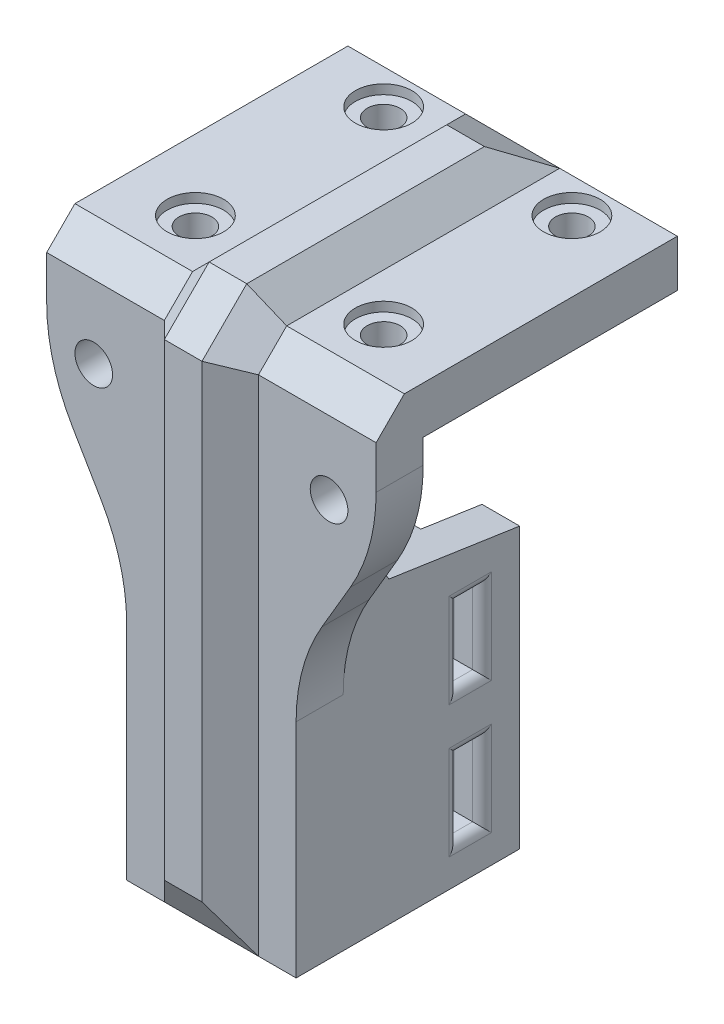
SolidWorks part; units mm, degrees
material "ABS"
ref_plane "Front Plane" through (0, 0, 0) normal (0, 0, 1) x (1, 0, 0)
ref_plane "Top Plane" through (0, 0, 0) normal (0, 1, 0) x (1, 0, 0)
ref_plane "Right Plane" through (0, 0, 0) normal (1, 0, 0) x (0, 0, -1)
sketch "Sketch1" plane through (0, 0, 0) normal (1, 0, 0) x (0, 0, -1)
  line L0 (0, 0) -> (0, -56.5)
  line L1 (0, 0) -> (32, 0)
  line L2 (32, 0) -> (32, -5)
  line L3 (32, -5) -> (5, -5)
  line L4 (5, -5) -> (5, -56.5)
  line L5 (5, -56.5) -> (0, -56.5)
  dimension "D1" = 5
  dimension "D2" = 27
  dimension "D3" = 51.5
extrude "Boss-Extrude1" add sketch "Sketch1" along normal blind 17.5 and the other way blind 17.5
sketch "Sketch2" plane through (0, 0, -5) normal (0, 0, -1) x (-1, 0, 0)
  line L0 (-39.6629, -48.5) -> (3.2968, -48.5) construction
  line L1 (-17.5, -5) -> (17.5, -5) construction
  line L2 (3.2968, -34.5) -> (-37.6565, -34.5) construction
  line L3 (-24.2611, -24) -> (31.917, -24) construction
  line L4 (-17.5, -56.5) -> (-17.5, -5) construction
  line L5 (-17.5, -27.5) -> (17.5, -27.5)
  line L6 (-17.5, -27.5) -> (-17.5, -56.5)
  line L7 (-17.5, -56.5) -> (17.5, -56.5)
  line L8 (17.5, -27.5) -> (17.5, -56.5)
  dimension "D1" = 14
  dimension "D2" = 43.5
  dimension "D3" = 19
  dimension "D4" = 7
extrude "Boss-Extrude2" add sketch "Sketch2" along normal blind 23.5
sketch "Sketch3" plane through (17.5, 0, 0) normal (1, 0, 0) x (0, 0, -1)
  line L0 (5, -27.5) -> (5, -5) construction
  line L1 (17.25, -30.5) -> (19.75, -30.5)
  line L2 (17.25, -30.5) -> (17.25, -38.5)
  line L3 (17.25, -38.5) -> (19.75, -38.5)
  line L4 (19.75, -30.5) -> (19.75, -38.5)
  line L5 (17.25, -30.5) -> (19.75, -38.5) construction
  line L6 (17.25, -38.5) -> (19.75, -30.5) construction
  line L7 (17.25, -44.5) -> (19.75, -44.5)
  line L8 (17.25, -44.5) -> (17.25, -52.5)
  line L9 (17.25, -52.5) -> (19.75, -52.5)
  line L10 (19.75, -44.5) -> (19.75, -52.5)
  line L11 (17.25, -44.5) -> (19.75, -52.5) construction
  line L12 (17.25, -52.5) -> (19.75, -44.5) construction
  line L13 (5, -5) -> (32, -5) construction
  point P0 (18.5, -34.5)
  point P5 (18.5, -48.5)
  dimension "D1" = 13.5
  dimension "D2" = 14
  dimension "D3" = 43.5
  dimension "D4" = 2.5
  dimension "D5" = 8
extrude "Cut-Extrude1" cut sketch "Sketch3" against normal through all
sketch "Sketch4" plane through (0, 0, -28.5) normal (0, 0, -1) x (-1, 0, 0)
  line L0 (-17.5, -27.5) -> (17.5, -27.5) construction
  line L1 (-5, -27.5) -> (5, -27.5)
  line L2 (-5, -27.5) -> (-5, -56.5)
  line L3 (-5, -56.5) -> (5, -56.5)
  line L4 (5, -27.5) -> (5, -56.5)
  line L5 (-17.5, -56.5) -> (17.5, -56.5) construction
  line L6 (-17.5, 0) -> (17.5, 0) construction
  point P8 (0, -27.5)
  point P11 (0, 0)
  dimension "D1" = 10
extrude "Cut-Extrude2" cut sketch "Sketch4" against normal up to surface (11.25 mm away) up to face at (0, -34.5, -17.25)
sketch "Sketch5" plane through (0, 0, -28.5) normal (0, 0, -1) x (-1, 0, 0)
  line L0 (-9, -27.5) -> (-9, -56.5)
  line L1 (-17.5, -27.5) -> (17.5, -27.5) construction
  line L2 (-17.5, -56.5) -> (17.5, -56.5) construction
  line L3 (-9, -56.5) -> (-17.5, -56.5)
  line L4 (-17.5, -56.5) -> (-17.5, -13)
  line L5 (-17.5, -27.5) -> (-17.5, -5) construction
  line L6 (-17.5, -13) -> (-9, -27.5)
  line L7 (-17.5, -5) -> (17.5, -5) construction
  line L8 (-5, -27.5) -> (-5, -56.5) construction
  line L9 (0, -12.0262) -> (0, -39.653) construction
  line L10 (-17.5, -5) -> (17.5, -5) construction
  line L11 (17.5, -56.5) -> (17.5, -13)
  line L12 (9, -56.5) -> (17.5, -56.5)
  line L13 (9, -27.5) -> (9, -56.5)
  line L14 (17.5, -13) -> (9, -27.5)
  point P20 (0, -5)
  dimension "D1" = 8
  dimension "D2" = 4
extrude "Cut-Extrude3" cut sketch "Sketch5" against normal through all
fillet "Fillet1" radius 20 4 edges at (-17.5, -13, -2.5) (17.5, -13, -2.5) (-9, -27.5, -2.5) (9, -27.5, -2.5)
sketch "Sketch6" plane through (0, 0, -17.25) normal (0, 0, -1) x (-1, 0, 0)
  line L0 (-17.5, -5) -> (17.5, -5) construction
  line L1 (-9, -56.5) -> (-9, -27.5) construction
  circle A0 centre (0, -42) radius 2
  point P5 (0, -5)
  point P8 (-9, -42)
  dimension "D1" = 4
extrude "Cut-Extrude4" cut sketch "Sketch6" against normal offset from surface (15.25 mm away) 2 up to face at (0, -22.9167, 0)
sketch "Sketch7" plane through (0, 0, 0) normal (0, 1, 0) x (1, 0, 0)
  line L0 (17.5, 5) -> (-17.5, 5) construction
  line L1 (-10, 28.3) -> (10, 28.3) construction
  line L2 (-10, 28.3) -> (-10, 8.3) construction
  line L3 (-10, 8.3) -> (10, 8.3) construction
  line L4 (10, 28.3) -> (10, 8.3) construction
  line L5 (-10, 28.3) -> (10, 8.3) construction
  line L6 (-10, 8.3) -> (10, 28.3) construction
  line L7 (17.5, 0) -> (-17.5, 0) construction
  circle A0 centre (10, 28.3) radius 1.75
  circle A1 centre (10, 8.3) radius 1.75
  circle A2 centre (-10, 8.3) radius 1.75
  circle A3 centre (-10, 28.3) radius 1.75
  point P0 (0, 18.3)
  point P10 (0, 0)
  dimension "D4" = 3.5
  dimension "D1" = 3.3
  dimension "D2" = 20
  dimension "D3" = 20
extrude "Cut-Extrude5" cut sketch "Sketch7" against normal up to next
sketch "Sketch8" plane through (0, 0, 0) normal (0, 1, 0) x (1, 0, 0)
  circle A0 centre (10, 28.3) radius 3
  circle A1 centre (10, 8.3) radius 3
  circle A2 centre (-10, 8.3) radius 3
  circle A3 centre (-10, 28.3) radius 3
  dimension "D1" = 6
extrude "Cut-Extrude6" cut sketch "Sketch8" against normal blind 1
sketch "Sketch9" plane through (0, 0, 0) normal (-1, 0, 0) x (0, 0, 1)
  line L0 (-32, 0) -> (0, 0)
  line L1 (0, 0) -> (0, -56.5)
  line L2 (0, -56.5) -> (3, -56.5)
  line L3 (3, -56.5) -> (3, 3)
  line L4 (3, 3) -> (-32, 3)
  line L5 (-32, 3) -> (-32, 0)
  dimension "D1" = 3
extrude "Boss-Extrude4" add sketch "Sketch9" along normal blind 2 and the other way blind 2
chamfer "Chamfer1" distance 3 distance2 5 1 edges at (0, 3, -32) first distance on face at (0, -0.5, -32)
chamfer "Chamfer2" distance 5 distance2 3 1 edges at (0, -56.5, 3) first distance on face at (0, -26.75, 3)
chamfer "Chamfer3" distance 3 distance2 3 3 edges at (0, 3, 3) (9.75, 0, 0) (-9.75, 0, 0)
chamfer "Chamfer4" distance 3 angle 45 6 edges at (-2, -29.75, 0) (-2, -1.5, -1.5) (-2, 0, -17.5) (2, -29.75, 0) (2, -1.5, -1.5) (2, 0, -17.5)
sketch "Sketch10" plane through (-2, 0, 0) normal (-1, 0, 0) x (0, 0, 1)
  line L0 (-1.7574, 3) -> (3, -1.7574)
  line L1 (3, -1.7574) -> (3, 0)
  line L2 (3, 0) -> (0, 3)
  line L3 (0, 3) -> (-1.7574, 3)
extrude "Cut-Extrude7" cut sketch "Sketch10" against normal up to next
sketch "Sketch11" plane through (-9, 0, 0) normal (-1, 0, 0) x (0, 0, 1)
  line L0 (-28.5, -27.5) -> (-5, -27.5) construction
  line L1 (-5, -7.57) -> (-5, -17.6844) construction
  line L2 (-32, -5) -> (-5, -5) construction
  line L3 (-32, -5) -> (-32, -13) construction
  line L4 (-32, -13) -> (-5, -13) construction
  line L5 (-5, -5) -> (-5, -13) construction
  line L6 (-5, -27.5) -> (-5, -16.5)
  line L7 (-24.5, -18) -> (-12.5, -18) construction
  line L8 (-24.5, -18) -> (-24.5, -8.5119) construction
  line L9 (-24.5, -8.5119) -> (-12.5, -8.5119) construction
  line L10 (-12.5, -18) -> (-12.5, -8.5119) construction
  line L11 (-24.5, -18) -> (-12.5, -8.5119) construction
  line L12 (-24.5, -8.5119) -> (-12.5, -18) construction
  line L13 (-25.5, -24) -> (-11.5, -24) construction
  line L14 (-25.5, -24) -> (-25.5, -15.5982) construction
  line L15 (-25.5, -15.5982) -> (-11.5, -15.5982) construction
  line L16 (-11.5, -24) -> (-11.5, -15.5982) construction
  line L17 (-25.5, -24) -> (-11.5, -15.5982) construction
  line L18 (-25.5, -15.5982) -> (-11.5, -24) construction
  line L19 (-5, -16.5) -> (-9.8595, -24.7238)
  line L20 (-28.5, -27.5) -> (-9.8595, -24.7238)
  line L21 (-28.5, -27.5) -> (-5, -27.5)
  point P11 (-18.5, -13.256)
  point P16 (-18.5, -19.7991)
  point P22 (-18.5, -5)
  line M4 (-5, -27.5) -> (-28.5, -27.5)
  dimension "D1" = 8
  dimension "D2" = 13
  dimension "D3" = 19
  dimension "D4" = 14
  dimension "D5" = 12
  dimension "D6" = 3.5
extrude "Boss-Extrude5" add sketch "Sketch11" against normal up to surface (18 mm away) contours L20 L6 L19 M4 region at (-9, -24.9233, -10.9255) up to face at (9, -38.9767, -11.1667)
sketch "Sketch12" plane through (0, -27.5, 0) normal (0, -1, 0) x (1, 0, 0)
  line L1 (5, -28.5) -> (-5, -28.5)
  line L2 (5, -28.5) -> (5, -17.25)
  line L3 (5, -17.25) -> (-5, -17.25)
  line L4 (-5, -28.5) -> (-5, -17.25)
extrude "Cut-Extrude8" cut sketch "Sketch12" against normal blind 2
fillet "Fillet2" radius 1 28 edges at (5, -52.5, -18.5) (5, -48.5, -19.75) (5, -44.5, -18.5) (5, -38.5, -18.5) (5, -34.5, -19.75) (5, -30.5, -18.5) (9, -38.5, -18.5) (9, -34.5, -17.25) (9, -34.5, -19.75) (9, -30.5, -18.5) (9, -44.5, -18.5) (9, -48.5, -17.25) (9, -52.5, -18.5) (9, -48.5, -19.75) (-5, -44.5, -18.5) (-5, -48.5, -19.75) (-5, -52.5, -18.5) (-5, -38.5, -18.5) (-5, -34.5, -19.75) (-5, -30.5, -18.5) (-9, -52.5, -18.5) (-9, -48.5, -19.75) (-9, -44.5, -18.5) (-9, -48.5, -17.25) (-9, -34.5, -17.25) (-9, -30.5, -18.5) (-9, -34.5, -19.75) (-9, -38.5, -18.5)
sketch "Sketch13" plane through (9, 0, 0) normal (1, 0, 0) x (0, 0, -1)
  line L1 (28.5, -56.5) -> (23.75, -56.5)
  line L2 (28.5, -56.5) -> (28.5, -24.4192)
  line L3 (28.5, -24.4192) -> (23.75, -24.4192)
  line L4 (23.75, -56.5) -> (23.75, -24.4192)
  line L6 (19.75, -52.5) -> (19.75, -44.5) construction
  dimension "D1" = 4
extrude "Cut-Extrude9" cut sketch "Sketch13" against normal through all
sketch "Sketch14" plane through (0, 0, -5) normal (0, 0, -1) x (-1, 0, 0)
  line L1 (-17.5, -5) -> (17.5, -5) construction
  line L3 (-9, -16.5) -> (-9, -5) construction
  line L4 (-17.5, -5) -> (17.5, -5) construction
  circle A0 centre (-12.5, -10.75) radius 2
  circle A1 centre (12.5, -10.75) radius 2
  point P10 (0, 0)
  dimension "D5" = 4
  dimension "D1" = 25
  dimension "D3" = 5.75
  dimension "D4" = 11.5
  dimension "D2" = 12.5
extrude "Cut-Extrude10" cut sketch "Sketch14" against normal up to next
equation "\"D3@Sketch14\"=\"D4@Sketch14\"/2"
